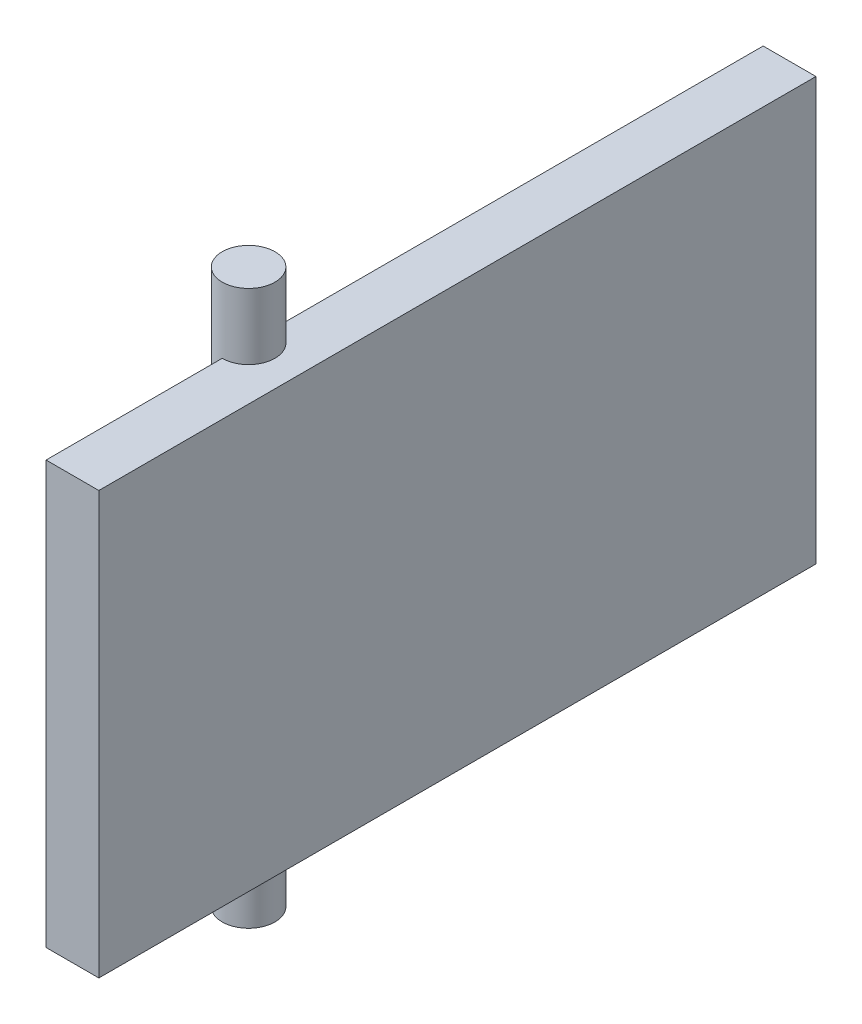
SolidWorks part; units mm, degrees
ref_plane "Front Plane" through (0, 0, 0) normal (0, 0, 1) x (1, 0, 0)
ref_plane "Top Plane" through (0, 0, 0) normal (0, 1, 0) x (1, 0, 0)
ref_plane "Right Plane" through (0, 0, 0) normal (1, 0, 0) x (0, 0, -1)
sketch "Sketch1" plane through (13.795, 0, 0) normal (1, 0, 0) x (0, 0, -1)
  line L0 (-33.175, 55.7847) -> (-33.175, 57.2847) construction
  line L1 (-23.175, 73.7847) -> (4, 73.7847)
  line L2 (-33.175, 73.7847) -> (-33.175, 57.7847) construction
  line L3 (-23.175, 57.7847) -> (4, 57.7847)
  line L4 (4, 73.7847) -> (4, 57.7847)
  line L5 (-34.175, 75.7847) -> (-30.175, 75.7847) construction
  line L6 (-24.175, 55.7847) -> (-23, 55.7847) construction
  line L7 (-23.175, 73.7847) -> (-23.175, 57.7847)
  line L8 (-18, 74.2847) -> (-18, 57.2847) construction
  line L9 (-33.175, 73.7847) -> (-23.175, 73.7847) construction
  line L10 (-33.175, 57.7847) -> (-23.175, 57.7847) construction
  dimension "D1" = 2
  dimension "D2" = 2
  dimension "D3" = 22
  dimension "D4" = 10
  dimension "D5" = 16
extrude "Boss-Extrude1" add sketch "Sketch1" along normal blind 2
sketch "Sketch2" plane through (0, 73.7847, 0) normal (0, 1, 0) x (1, 0, 0)
  circle A0 centre (13.795, -15.5) radius 1
  dimension "D1" = 2
extrude "Boss-Extrude2" add sketch "Sketch2" along normal mid plane 5
ref_plane "Plane1" through (0, 65.7847, 0) normal (0, 1, 0) x (1, 0, 0)
mirror "Mirror1" about plane through (0, 65.7847, 0) normal (0, 1, 0) of "Boss-Extrude2"
fillet "Fillet1" radius 1 2 edges at (13.795, 71.2847, 15.5) (13.795, 60.2847, 15.5)
